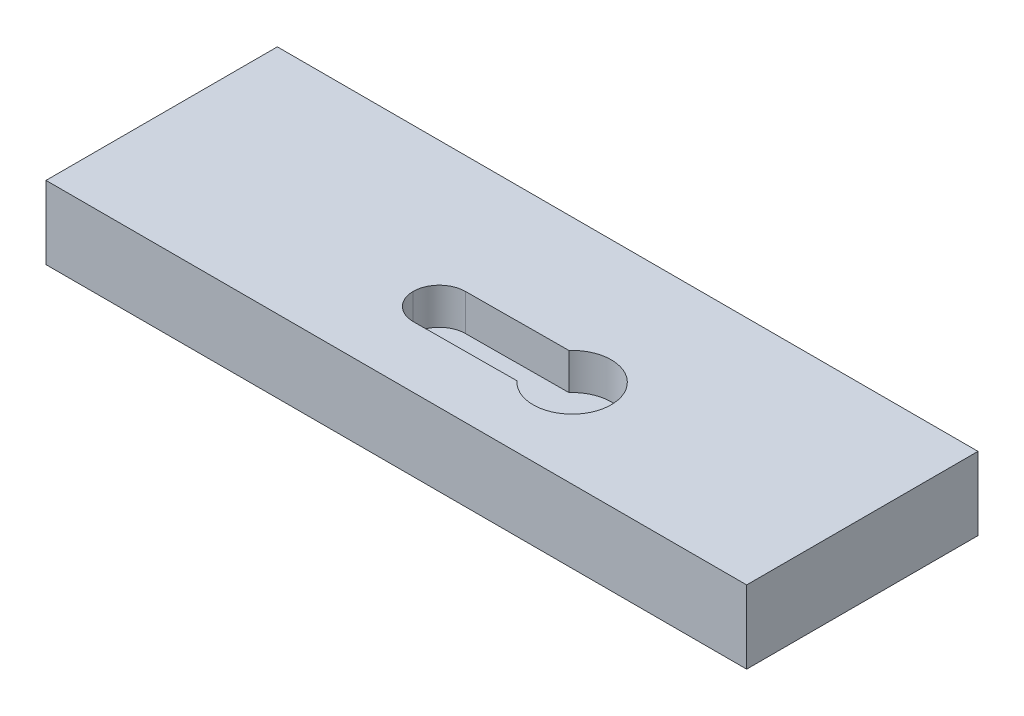
SolidWorks part; units mm, degrees
ref_plane "Front Plane" through (0, 0, 0) normal (0, 0, 1) x (1, 0, 0)
ref_plane "Top Plane" through (0, 0, 0) normal (0, 1, 0) x (1, 0, 0)
ref_plane "Right Plane" through (0, 0, 0) normal (1, 0, 0) x (0, 0, -1)
sketch "servo-arm" plane through (0, 139.2377, 0) normal (0, 1, 0) x (1, 0, 0)
  line L2 (9.9217, -56.3) -> (0.665, -56.356)
  line L3 (0.6849, -59.6325) -> (9.9415, -59.5765)
  line L4 (9.9217, -56.3) -> (0.665, -56.356) construction
  line L5 (0.6849, -59.6325) -> (9.9415, -59.5765) construction
  circle A0 centre (12.1555, -57.9248) radius 0.635 construction
  circle A1 centre (12.1555, -57.9248) radius 0.635 construction
  arc A3 (0.665, -56.356) -> (-0.976, -58.0042) centre (0.675, -58.007) ccw
  arc A4 (-0.976, -58.0042) -> (0.6849, -59.6325) centre (0.6749, -57.9816) ccw
  arc A5 (9.9415, -59.5765) -> (9.9217, -56.3) centre (12.1555, -57.9248) ccw
  arc A6 (0.665, -56.356) -> (-0.976, -58.0042) centre (0.675, -58.007) ccw construction
  arc A7 (-0.976, -58.0042) -> (0.6849, -59.6325) centre (0.6749, -57.9816) ccw construction
  arc A8 (9.9415, -59.5765) -> (9.9217, -56.3) centre (12.1555, -57.9248) ccw construction
  point P2 (12.1555, -57.9248)
  dimension "D1" = 0
ref_plane "bottom-servo" [suppressed] through (0, 135.8722, 0) normal (0, -1, 0) x (-1, 0, 0)
ref_plane "face-front" [suppressed] through (0, 129.5222, 0) normal (0, 1, 0) x (1, 0, 0)
ref_plane "servo-arm-front" through (0, 139.2377, 0) normal (0, 1, 0) x (1, 0, 0)
sketch "Sketch2" plane through (0, 139.2377, 0) normal (0, 1, 0) x (1, 0, 0)
  line L0 (-25.9445, -50.3048) -> (24.8555, -50.3048)
  line L1 (9.6173, -55.6668) -> (0.6612, -55.721) construction
  line L2 (9.9217, -56.3) -> (0.665, -56.356)
  line L3 (0.6849, -59.6325) -> (9.9415, -59.5765)
  line L4 (9.9217, -56.3) -> (0.665, -56.356) construction
  line L5 (0.6849, -59.6325) -> (9.9415, -59.5765) construction
  line L6 (-25.9445, -50.3048) -> (-25.9445, -63.0048)
  line L7 (-25.9445, -63.0048) -> (24.8555, -63.0048)
  line L8 (24.8555, -50.3048) -> (24.8555, -63.0048)
  line L9 (0.6887, -60.2675) -> (9.6448, -60.2133) construction
  arc A0 (0.6612, -55.721) -> (-1.611, -58.0081) centre (0.675, -58.007) ccw construction
  arc A1 (-1.611, -58.0081) -> (0.6887, -60.2675) centre (0.6749, -57.9816) ccw construction
  arc A2 (9.6448, -60.2133) -> (9.6173, -55.6668) centre (12.1555, -57.9248) ccw construction
  arc A3 (0.665, -56.356) -> (-0.976, -58.0042) centre (0.675, -58.007) ccw
  arc A4 (-0.976, -58.0042) -> (0.6849, -59.6325) centre (0.6749, -57.9816) ccw
  arc A5 (9.9415, -59.5765) -> (9.9217, -56.3) centre (12.1555, -57.9248) ccw
  arc A6 (0.665, -56.356) -> (-0.976, -58.0042) centre (0.675, -58.007) ccw construction
  arc A7 (-0.976, -58.0042) -> (0.6849, -59.6325) centre (0.6749, -57.9816) ccw construction
  arc A8 (9.9415, -59.5765) -> (9.9217, -56.3) centre (12.1555, -57.9248) ccw construction
  dimension "D2" = 12.7
  dimension "D3" = 12.7
  dimension "D4" = 38.1
  dimension "D5" = 5.08
  dimension "D1" = 0
  dimension "D6" = 0.635
extrude "Boss-Extrude1" add sketch "Sketch2" against normal blind 3.175
sketch "Sketch3" plane through (0, 139.2377, 0) normal (0, 1, 0) x (1, 0, 0)
  line L0 (9.6173, -55.6668) -> (0.6612, -55.721) construction
  line L1 (0.6887, -60.2675) -> (9.6448, -60.2133) construction
  line L2 (9.6173, -55.6668) -> (0.6612, -55.721)
  line L3 (0.6887, -60.2675) -> (9.6448, -60.2133)
  line L8 (35.0155, -65.601) -> (35.0155, -45.4744)
  line L10 (-25.9445, -45.4744) -> (-25.9445, -65.601)
  line L11 (-25.9445, -65.601) -> (35.0155, -65.601)
  line L26 (35.0155, -45.4744) -> (-25.9445, -45.4744)
  arc A0 (0.6612, -55.721) -> (-1.611, -58.0081) centre (0.675, -58.007) ccw construction
  arc A1 (-1.611, -58.0081) -> (0.6887, -60.2675) centre (0.6749, -57.9816) ccw construction
  arc A2 (9.6448, -60.2133) -> (9.6173, -55.6668) centre (12.1555, -57.9248) ccw construction
  arc A3 (0.6612, -55.721) -> (-1.611, -58.0081) centre (0.675, -58.007) ccw
  arc A4 (-1.611, -58.0081) -> (0.6887, -60.2675) centre (0.6749, -57.9816) ccw
  arc A5 (9.6448, -60.2133) -> (9.6173, -55.6668) centre (12.1555, -57.9248) ccw
  dimension "D1" = 60.96
  dimension "D2" = 20.1266
extrude "Boss-Extrude2" add sketch "Sketch3" along normal blind 3.175 and the other way up to surface (3.175 mm away) other way up to face at (-0.5445, 136.0627, 56.6548)
